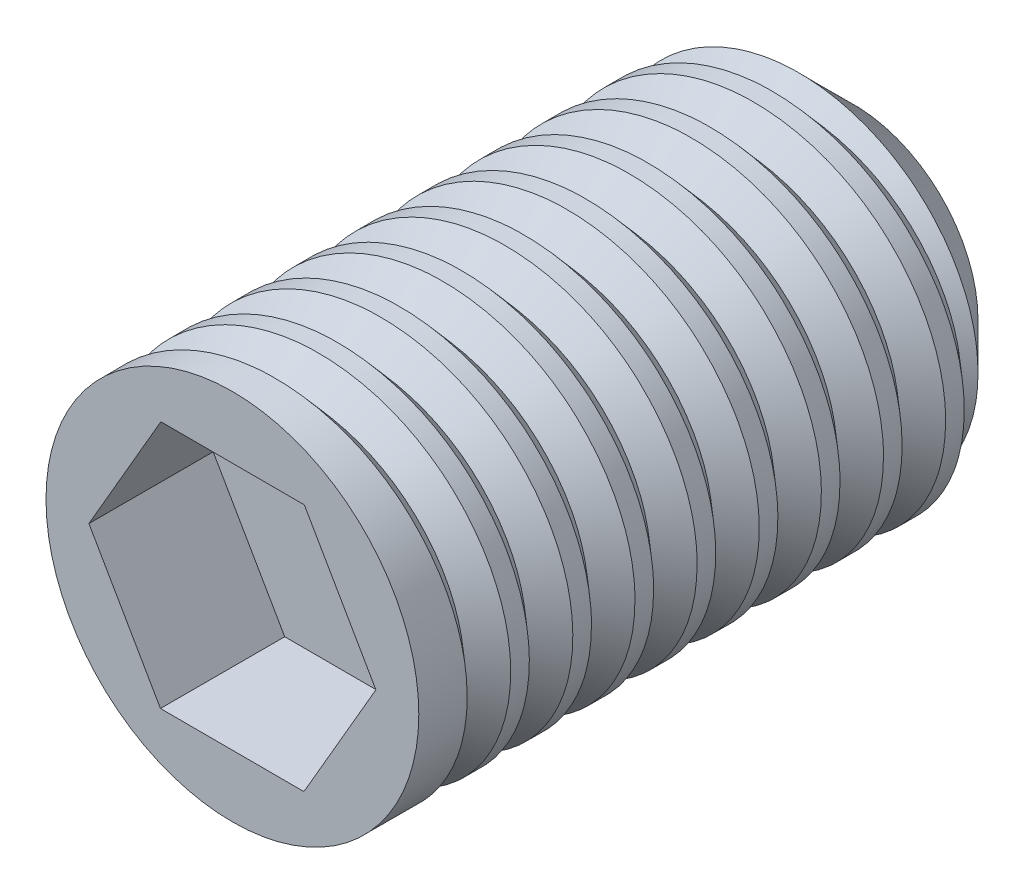
SolidWorks part; units mm, degrees
ref_plane "前视基准面" through (0, 0, 0) normal (0, 0, 1) x (1, 0, 0)
ref_plane "上视基准面" through (0, 0, 0) normal (0, 1, 0) x (1, 0, 0)
ref_plane "右视基准面" through (0, 0, 0) normal (1, 0, 0) x (0, 0, -1)
sketch "草图1" plane through (0, 0, 0) normal (0, 0, 1) x (1, 0, 0)
  circle A0 centre (0, 0) radius 3
  dimension "D1" = 6
extrude "凸台-拉伸1" add sketch "草图1" along normal blind 10
sketch "草图2" plane through (0, 0, 10) normal (0, 0, 1) x (1, 0, 0)
  line L1 (1.158, 1.9981) -> (-1.1514, 2.0019)
  line L2 (-1.1514, 2.0019) -> (-2.3094, 0.0039)
  line L3 (-2.3094, 0.0039) -> (-1.158, -1.9981)
  line L4 (-1.158, -1.9981) -> (1.1514, -2.0019)
  line L5 (1.1514, -2.0019) -> (2.3094, -0.0039)
  line L6 (2.3094, -0.0039) -> (1.158, 1.9981)
  circle A0 centre (0, 0) radius 2 construction
  dimension "D1" = 4
extrude "切除-拉伸1" cut sketch "草图2" against normal blind 2
chamfer "倒角1" distance 1 angle 45 1 edges at (3, 0, 0)
sketch "草图3" plane through (0, 0, 0) normal (0, 0, -1) x (-1, 0, 0)
  circle A0 centre (0, 0) radius 3
curve "螺旋线/涡状线1" pitch 1 height 9.5 radius 3 centre (0, 0, 0) axis (0, 0, 1) start towards (0.7071, 0.7071, 0)
sketch "草图4" plane through (0, 0, 0) normal (1, 0, 0) x (0, 0, -1)
  line L0 (-0.475, 3) -> (0.225, 3)
  line L1 (-0.125, 3) -> (-0.125, 2.6) construction
  line L2 (0.225, 3) -> (-0.125, 2.6)
  line L3 (-0.125, 2.6) -> (-0.475, 3)
  dimension "D1" = 0.7
  dimension "D2" = 0.4
sweep "切除-扫描1" cut profiles "草图4" path "螺旋线/涡状线1"
